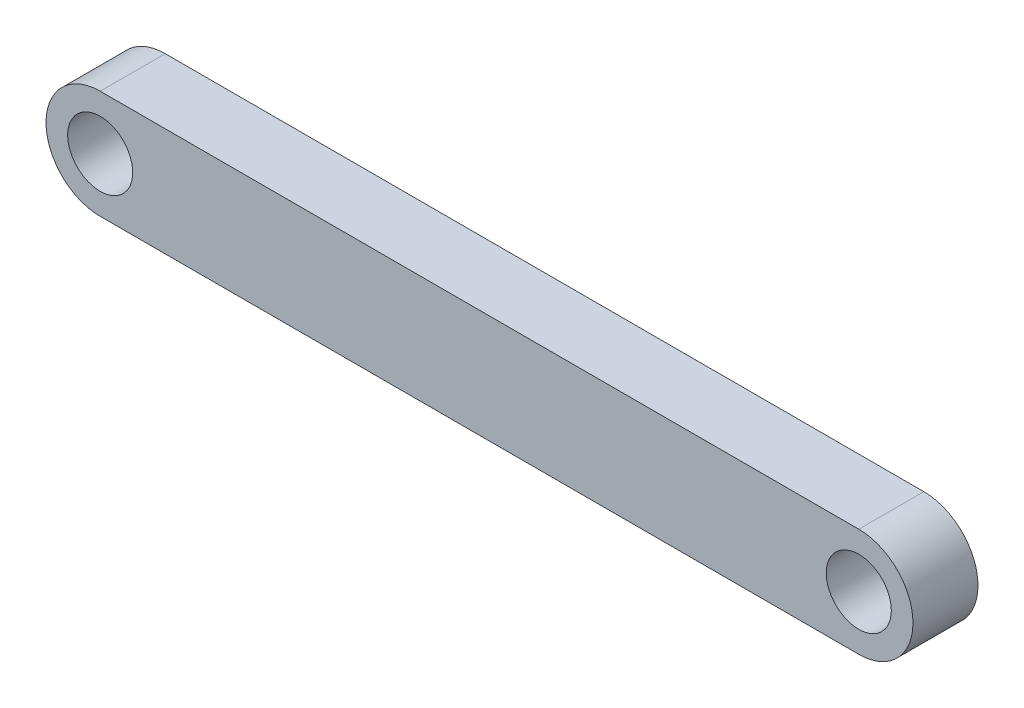
SolidWorks part; units mm, degrees
ref_plane "Ebene vorne" through (0, 0, 0) normal (0, 0, 1) x (1, 0, 0)
ref_plane "Ebene oben" through (0, 0, 0) normal (0, 1, 0) x (1, 0, 0)
ref_plane "Ebene rechts" through (0, 0, 0) normal (1, 0, 0) x (0, 0, -1)
sketch "Skizze1" plane through (0, 0, 0) normal (0, 0, 1) x (1, 0, 0)
  circle A0 centre (0, 670) radius 3.25
  circle A1 centre (70, 670) radius 3.25
sketch "Skizze2" plane through (0, 0, 0) normal (0, 0, 1) x (1, 0, 0)
  line L0 (0, 675) -> (70, 675)
  line L1 (0, 665) -> (70, 665)
  arc A0 (0, 675) -> (0, 665) centre (0, 670) ccw
  arc A1 (70, 665) -> (70, 675) centre (70, 670) ccw
  circle A2 centre (0, 670) radius 3
  circle A3 centre (70, 670) radius 3
  dimension "D1" = 10
extrude "Aufsatz-Linear austragen1" add sketch "Skizze2" along normal blind 3 and the other way blind 3
